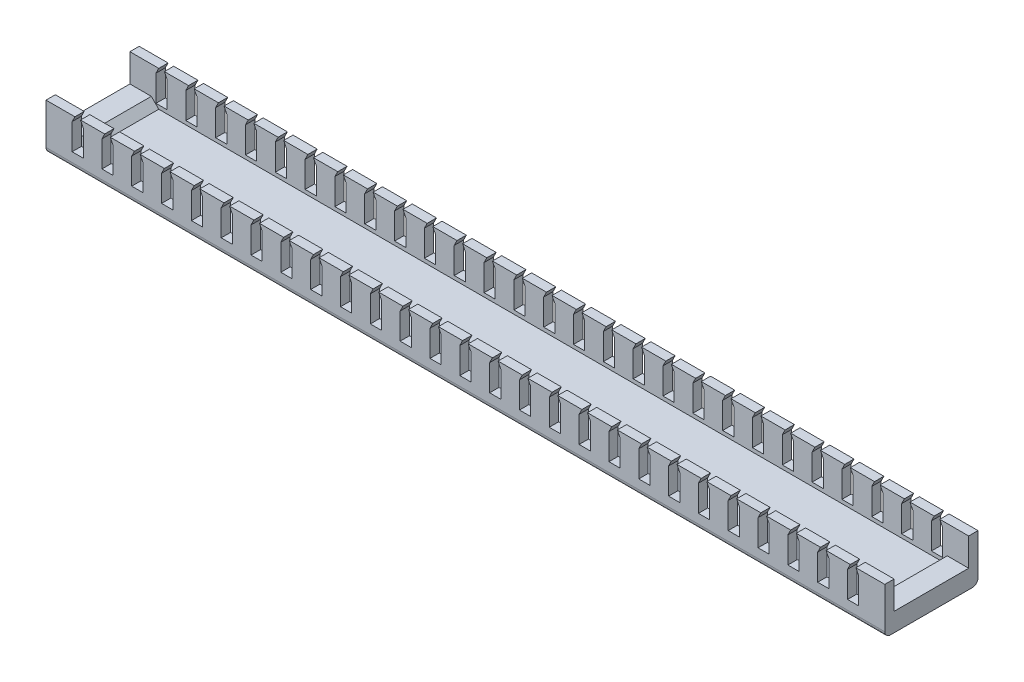
SolidWorks part; units mm, degrees
ref_plane "Front Plane" through (0, 0, 0) normal (0, 0, 1) x (1, 0, 0)
ref_plane "Top Plane" through (0, 0, 0) normal (0, 1, 0) x (1, 0, 0)
ref_plane "Right Plane" through (0, 0, 0) normal (1, 0, 0) x (0, 0, -1)
sketch "Sketch2" plane through (0, 0, 0) normal (1, 0, 0) x (0, 0, -1)
  line L0 (1.5, 0) -> (23.5, 0)
  line L1 (25, 1.5) -> (25, 12.5)
  line L2 (25, 12.5) -> (22.5, 12.5)
  line L3 (22.5, 12.5) -> (22.5, 3)
  line L4 (22.5, 3) -> (2.5, 3)
  line L5 (2.5, 3) -> (2.5, 12.5)
  line L6 (2.5, 12.5) -> (0, 12.5)
  line L7 (0, 12.5) -> (0, 1.5)
  arc A0 (23.5, 0) -> (25, 1.5) centre (23.5, 1.5) ccw
  arc A1 (1.5, 0) -> (0, 1.5) centre (1.5, 1.5) cw
  point P11 (25, 0)
  point P14 (0, 0)
  dimension "D5" = 1.5
  dimension "D1" = 12.5
  dimension "D2" = 3
  dimension "D3" = 25
  dimension "D4" = 2.5
extrude "ProfileBoss-Extrude1" add sketch "Sketch2" along normal blind 225
sketch "Sketch3" plane through (0, 0, 0) normal (0, 0, 1) x (1, 0, 0)
  line L0 (7.75, 12.5) -> (7, 11)
  line L1 (7, 11) -> (7, 4)
  line L2 (7, 4) -> (10, 4)
  line L3 (10, 4) -> (10, 11)
  line L4 (10, 11) -> (9.25, 12.5)
  line L5 (225, 12.5) -> (0, 12.5) construction
  line L6 (9.25, 12.5) -> (7.75, 12.5)
  line L7 (225, 0) -> (0, 0) construction
  line L8 (0, 12.5) -> (0, 1.5) construction
  line L9 (15.75, 12.5) -> (15, 11)
  line L10 (15, 11) -> (15, 4)
  line L11 (15, 4) -> (18, 4)
  line L12 (18, 4) -> (18, 11)
  line L13 (18, 11) -> (17.25, 12.5)
  line L14 (17.25, 12.5) -> (15.75, 12.5)
  line L15 (23.75, 12.5) -> (23, 11)
  line L16 (23, 11) -> (23, 4)
  line L17 (23, 4) -> (26, 4)
  line L18 (26, 4) -> (26, 11)
  line L19 (26, 11) -> (25.25, 12.5)
  line L20 (25.25, 12.5) -> (23.75, 12.5)
  line L21 (31.75, 12.5) -> (31, 11)
  line L22 (31, 11) -> (31, 4)
  line L23 (31, 4) -> (34, 4)
  line L24 (34, 4) -> (34, 11)
  line L25 (34, 11) -> (33.25, 12.5)
  line L26 (33.25, 12.5) -> (31.75, 12.5)
  line L27 (39.75, 12.5) -> (39, 11)
  line L28 (39, 11) -> (39, 4)
  line L29 (39, 4) -> (42, 4)
  line L30 (42, 4) -> (42, 11)
  line L31 (42, 11) -> (41.25, 12.5)
  line L32 (41.25, 12.5) -> (39.75, 12.5)
  line L33 (47.75, 12.5) -> (47, 11)
  line L34 (47, 11) -> (47, 4)
  line L35 (47, 4) -> (50, 4)
  line L36 (50, 4) -> (50, 11)
  line L37 (50, 11) -> (49.25, 12.5)
  line L38 (49.25, 12.5) -> (47.75, 12.5)
  line L39 (55.75, 12.5) -> (55, 11)
  line L40 (55, 11) -> (55, 4)
  line L41 (55, 4) -> (58, 4)
  line L42 (58, 4) -> (58, 11)
  line L43 (58, 11) -> (57.25, 12.5)
  line L44 (57.25, 12.5) -> (55.75, 12.5)
  line L45 (63.75, 12.5) -> (63, 11)
  line L46 (63, 11) -> (63, 4)
  line L47 (63, 4) -> (66, 4)
  line L48 (66, 4) -> (66, 11)
  line L49 (66, 11) -> (65.25, 12.5)
  line L50 (65.25, 12.5) -> (63.75, 12.5)
  line L51 (71.75, 12.5) -> (71, 11)
  line L52 (71, 11) -> (71, 4)
  line L53 (71, 4) -> (74, 4)
  line L54 (74, 4) -> (74, 11)
  line L55 (74, 11) -> (73.25, 12.5)
  line L56 (73.25, 12.5) -> (71.75, 12.5)
  line L57 (79.75, 12.5) -> (79, 11)
  line L58 (79, 11) -> (79, 4)
  line L59 (79, 4) -> (82, 4)
  line L60 (82, 4) -> (82, 11)
  line L61 (82, 11) -> (81.25, 12.5)
  line L62 (81.25, 12.5) -> (79.75, 12.5)
  line L63 (87.75, 12.5) -> (87, 11)
  line L64 (87, 11) -> (87, 4)
  line L65 (87, 4) -> (90, 4)
  line L66 (90, 4) -> (90, 11)
  line L67 (90, 11) -> (89.25, 12.5)
  line L68 (89.25, 12.5) -> (87.75, 12.5)
  line L69 (95.75, 12.5) -> (95, 11)
  line L70 (95, 11) -> (95, 4)
  line L71 (95, 4) -> (98, 4)
  line L72 (98, 4) -> (98, 11)
  line L73 (98, 11) -> (97.25, 12.5)
  line L74 (97.25, 12.5) -> (95.75, 12.5)
  line L75 (103.75, 12.5) -> (103, 11)
  line L76 (103, 11) -> (103, 4)
  line L77 (103, 4) -> (106, 4)
  line L78 (106, 4) -> (106, 11)
  line L79 (106, 11) -> (105.25, 12.5)
  line L80 (105.25, 12.5) -> (103.75, 12.5)
  line L81 (111.75, 12.5) -> (111, 11)
  line L82 (111, 11) -> (111, 4)
  line L83 (111, 4) -> (114, 4)
  line L84 (114, 4) -> (114, 11)
  line L85 (114, 11) -> (113.25, 12.5)
  line L86 (113.25, 12.5) -> (111.75, 12.5)
  line L87 (119.75, 12.5) -> (119, 11)
  line L88 (119, 11) -> (119, 4)
  line L89 (119, 4) -> (122, 4)
  line L90 (122, 4) -> (122, 11)
  line L91 (122, 11) -> (121.25, 12.5)
  line L92 (121.25, 12.5) -> (119.75, 12.5)
  line L93 (127.75, 12.5) -> (127, 11)
  line L94 (127, 11) -> (127, 4)
  line L95 (127, 4) -> (130, 4)
  line L96 (130, 4) -> (130, 11)
  line L97 (130, 11) -> (129.25, 12.5)
  line L98 (129.25, 12.5) -> (127.75, 12.5)
  line L99 (135.75, 12.5) -> (135, 11)
  line L100 (135, 11) -> (135, 4)
  line L101 (135, 4) -> (138, 4)
  line L102 (138, 4) -> (138, 11)
  line L103 (138, 11) -> (137.25, 12.5)
  line L104 (137.25, 12.5) -> (135.75, 12.5)
  line L105 (143.75, 12.5) -> (143, 11)
  line L106 (143, 11) -> (143, 4)
  line L107 (143, 4) -> (146, 4)
  line L108 (146, 4) -> (146, 11)
  line L109 (146, 11) -> (145.25, 12.5)
  line L110 (145.25, 12.5) -> (143.75, 12.5)
  line L111 (151.75, 12.5) -> (151, 11)
  line L112 (151, 11) -> (151, 4)
  line L113 (151, 4) -> (154, 4)
  line L114 (154, 4) -> (154, 11)
  line L115 (154, 11) -> (153.25, 12.5)
  line L116 (153.25, 12.5) -> (151.75, 12.5)
  line L117 (159.75, 12.5) -> (159, 11)
  line L118 (159, 11) -> (159, 4)
  line L119 (159, 4) -> (162, 4)
  line L120 (162, 4) -> (162, 11)
  line L121 (162, 11) -> (161.25, 12.5)
  line L122 (161.25, 12.5) -> (159.75, 12.5)
  line L123 (167.75, 12.5) -> (167, 11)
  line L124 (167, 11) -> (167, 4)
  line L125 (167, 4) -> (170, 4)
  line L126 (170, 4) -> (170, 11)
  line L127 (170, 11) -> (169.25, 12.5)
  line L128 (169.25, 12.5) -> (167.75, 12.5)
  line L129 (175.75, 12.5) -> (175, 11)
  line L130 (175, 11) -> (175, 4)
  line L131 (175, 4) -> (178, 4)
  line L132 (178, 4) -> (178, 11)
  line L133 (178, 11) -> (177.25, 12.5)
  line L134 (177.25, 12.5) -> (175.75, 12.5)
  line L135 (183.75, 12.5) -> (183, 11)
  line L136 (183, 11) -> (183, 4)
  line L137 (183, 4) -> (186, 4)
  line L138 (186, 4) -> (186, 11)
  line L139 (186, 11) -> (185.25, 12.5)
  line L140 (185.25, 12.5) -> (183.75, 12.5)
  line L141 (191.75, 12.5) -> (191, 11)
  line L142 (191, 11) -> (191, 4)
  line L143 (191, 4) -> (194, 4)
  line L144 (194, 4) -> (194, 11)
  line L145 (194, 11) -> (193.25, 12.5)
  line L146 (193.25, 12.5) -> (191.75, 12.5)
  line L147 (199.75, 12.5) -> (199, 11)
  line L148 (199, 11) -> (199, 4)
  line L149 (199, 4) -> (202, 4)
  line L150 (202, 4) -> (202, 11)
  line L151 (202, 11) -> (201.25, 12.5)
  line L152 (201.25, 12.5) -> (199.75, 12.5)
  line L153 (207.75, 12.5) -> (207, 11)
  line L154 (207, 11) -> (207, 4)
  line L155 (207, 4) -> (210, 4)
  line L156 (210, 4) -> (210, 11)
  line L157 (210, 11) -> (209.25, 12.5)
  line L158 (209.25, 12.5) -> (207.75, 12.5)
  line L159 (215.75, 12.5) -> (215, 11)
  line L160 (215, 11) -> (215, 4)
  line L161 (215, 4) -> (218, 4)
  line L162 (218, 4) -> (218, 11)
  line L163 (218, 11) -> (217.25, 12.5)
  line L164 (217.25, 12.5) -> (215.75, 12.5)
  line L255 (225, 12.5) -> (225, 1.5) construction
  point P12 (218, 7.5)
  dimension "D1" = 3
  dimension "D2" = 1.5
  dimension "D3" = 4
  dimension "D5" = 7
  dimension "D4" = 1.5
  dimension "D7" = 225
  dimension "D8" = 5
  dimension "D9" = 7
  dimension "D6" = 27
extrude "SpikesCut-Extrude1" cut sketch "Sketch3" against normal through all
sketch "MountHoleThicknessSketch4" plane through (0, 3, 0) normal (0, 1, 0) x (1, 0, 0)
  line L0 (0, 22.5) -> (0, 2.5) construction
  line L1 (0, 22.5) -> (7.75, 22.5)
  line L2 (0, 22.5) -> (0, 2.5)
  line L3 (0, 2.5) -> (7.75, 2.5)
  line L4 (7.75, 22.5) -> (7.75, 2.5)
  line L5 (225, 2.5) -> (0, 2.5) construction
  line L6 (7.75, 22.5) -> (0, 22.5) construction
  line L7 (7, 2.5) -> (10, 2.5) construction
  line L8 (7.75, 2.5) -> (7.75, 0) construction
  line L10 (225, 22.5) -> (217.25, 22.5)
  line L11 (225, 22.5) -> (225, 2.5)
  line L12 (225, 2.5) -> (217.25, 2.5)
  line L13 (217.25, 22.5) -> (217.25, 2.5)
extrude "MountHolesThicknessBoss-Extrude1" add sketch "MountHoleThicknessSketch4" along normal blind 2
sketch "MountHolesSketch5" plane through (0, 3, 0) normal (0, 1, 0) x (1, 0, 0)
  line L0 (0, 22.5) -> (0, 2.5) construction
  line L1 (225, 22.5) -> (225, 2.5) construction
  line L2 (7.75, 0) -> (0, 0) construction
  circle A0 centre (5, 12.5) radius 2.05
  circle A1 centre (220, 12.5) radius 2.05
  point P11 (3.875, 0)
  dimension "D1" = 4.1
  dimension "D2" = 5
  dimension "D3" = 5
  dimension "D4" = 12.5
  dimension "D5" = 215
extrude "MountHolesCut-Extrude2" cut sketch "MountHolesSketch5" against normal blind 4
chamfer "Chamfer1" distance 2 angle 45 2 edges at (217.25, 5, -12.5) (7.75, 5, -12.5)
equation "\"SerratedChannelWidth\"= 25mm"
equation "\"D3@Sketch2\"=\"SerratedChannelWidth\""
equation "\"SerratedChannelHeight\"= 12.5mm"
equation "\"D1@Sketch2\"=\"SerratedChannelHeight\""
equation "\"SerratedChannelBaseHeight\"= 3mm"
equation "\"D2@Sketch2\"=\"SerratedChannelBaseHeight\""
equation "\"SerratedChannelChannelProngWidth\"= 2.5mm"
equation "\"D4@Sketch2\"=\"SerratedChannelChannelProngWidth\""
equation "\"SerratedChannelLength\"= 225mm"
equation "\"D1@ProfileBoss-Extrude1\"=\"SerratedChannelLength\""
equation "\"SerratedChannelProngOpenningWidth\"= 3mm"
equation "\"D1@Sketch3\"=\"SerratedChannelProngOpenningWidth\""
equation "\"SerratedChannelProngBaseHeight\"= 4mm"
equation "\"D3@Sketch3\"=\"SerratedChannelProngBaseHeight\""
equation "\"SerratedChannelProngHookSize\"= 1.5mm"
equation "\"D4@Sketch3\"=\"SerratedChannelProngHookSize\""
equation "\"D2@Sketch3\"=\"SerratedChannelProngHookSize\""
equation "\"SerratedChannelProngClosedWidth\"= 5mm"
equation "\"D8@Sketch3\"=\"SerratedChannelProngClosedWidth\""
equation "\"SerratedChannelStartOffset\"=7"
equation "\"M3HeatInsertHoleDepth\"= 4mm"
equation "\"M3HeatInsertHoleDiameter\"= 4mm + .1mm'Add .1mm for printing"
equation "\"D1@MountHolesCut-Extrude2\"=\"M3HeatInsertHoleDepth\""
equation "\"D1@MountHolesSketch5\"=\"M3HeatInsertHoleDiameter\""
equation "\"D4@MountHolesSketch5\"=\"SerratedChannelWidth\"/2"
